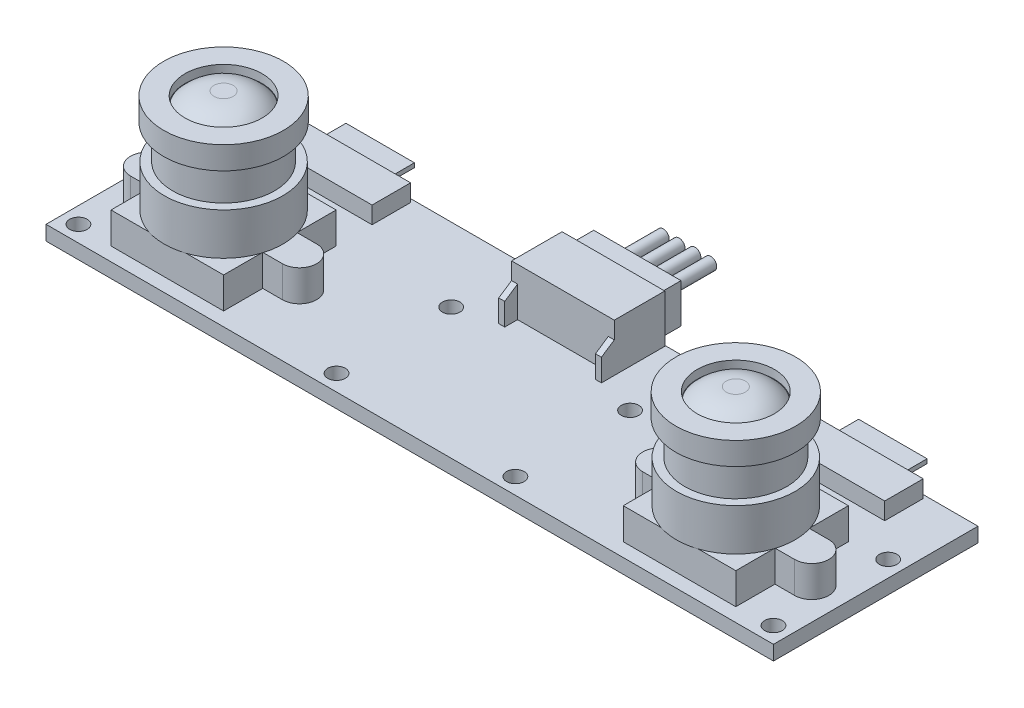
SolidWorks part; units mm, degrees
ref_plane "Front" through (0, 0, 0) normal (0, 0, 1) x (1, 0, 0)
ref_plane "Top" through (0, 0, 0) normal (0, 1, 0) x (1, 0, 0)
ref_plane "Right" through (0, 0, 0) normal (1, 0, 0) x (0, 0, -1)
sketch "Sketch1" plane through (0, 0, 0) normal (0, 1, 0) x (1, 0, 0)
  line L1 (-42.5, -11.95) -> (42.5, -11.95)
  line L2 (-42.5, -11.95) -> (-42.5, 11.95)
  line L3 (-42.5, 11.95) -> (42.5, 11.95)
  line L4 (42.5, -11.95) -> (42.5, 11.95)
  line L5 (-42.5, -11.95) -> (42.5, 11.95) construction
  line L6 (-42.5, 11.95) -> (42.5, -11.95) construction
  point P0 (0, 0)
  dimension "D1" = 23.9
  dimension "D2" = 85
extrude "Boss-Extrude1" add sketch "Sketch1" along normal blind 1.7
sketch "Sketch2" plane through (0, 1.7, 0) normal (0, 1, 0) x (1, 0, 0)
  line L0 (40.605, -11.08) -> (40.605, -11.95) construction
  line L1 (-40.605, -10.055) -> (40.605, -10.055) construction
  line L2 (-40.605, -10.055) -> (-40.605, 3.345) construction
  line L3 (-40.605, 3.345) -> (40.605, 3.345) construction
  line L5 (-40.605, -10.055) -> (40.605, 3.345) construction
  line L6 (-40.605, 3.345) -> (40.605, -10.055) construction
  line L7 (-10.45, -10.055) -> (10.45, -10.055) construction
  line L8 (-10.45, -10.055) -> (-10.45, 3.345) construction
  line L9 (-10.45, 3.345) -> (10.45, 3.345) construction
  line L10 (10.45, -10.055) -> (10.45, 3.345) construction
  line L11 (-10.45, -10.055) -> (10.45, 3.345) construction
  line L12 (-10.45, 3.345) -> (10.45, -10.055) construction
  line L14 (-42.5, -11.95) -> (42.5, -11.95) construction
  line L16 (41.63, -10.055) -> (42.5, -10.055) construction
  line L17 (42.5, -11.95) -> (42.5, 11.95) construction
  line L18 (-9.425, 3.345) -> (9.425, 3.345) construction
  line L19 (40.605, 2.32) -> (40.605, -9.03) construction
  circle A0 centre (-40.605, 3.345) radius 1.025
  circle A1 centre (-10.45, 3.345) radius 1.025
  circle A2 centre (-40.605, -10.055) radius 1.025
  circle A3 centre (-10.45, -10.055) radius 1.025
  circle A4 centre (10.45, 3.345) radius 1.025
  circle A5 centre (40.605, 3.345) radius 1.025
  circle A6 centre (40.605, -10.055) radius 1.025
  circle A7 centre (10.45, -10.055) radius 1.025
  point P0 (0, -3.355)
  point P5 (0, -3.355)
  dimension "D1" = 2.05
  dimension "D2" = 0.87
  dimension "D3" = 18.85
  dimension "D4" = 11.35
extrude "Cut-Extrude1" cut sketch "Sketch2" against normal through all
sketch "Sketch3" plane through (0, 1.7, 0) normal (0, 1, 0) x (1, 0, 0)
  line L0 (42.5, 11.95) -> (-42.5, 11.95) construction
  line L1 (-6, 5.95) -> (6, 5.95)
  line L2 (-6, 5.95) -> (-6, 11.95)
  line L3 (-6, 11.95) -> (6, 11.95)
  line L4 (6, 5.95) -> (6, 11.95)
  line L5 (-6, 5.95) -> (6, 11.95) construction
  line L6 (-6, 11.95) -> (6, 5.95) construction
  point P0 (0, 8.95)
  point P7 (6.8289, 3.9107)
  point P8 (0, 0)
  point P10 (6.1915, 4.9199)
  dimension "D1" = 12
  dimension "D2" = 6
extrude "Boss-Extrude2" add sketch "Sketch3" along normal blind 5.6
sketch "Sketch4" plane through (0, 1.7, 0) normal (0, 1, 0) x (1, 0, 0)
  line L1 (-6, 5.95) -> (-5.3, 5.95)
  line L2 (-6, 5.95) -> (-6, 4.45)
  line L3 (-6, 4.45) -> (-5.3, 4.45)
  line L4 (-5.3, 5.95) -> (-5.3, 4.45)
  line L5 (6, 5.95) -> (5.3, 5.95)
  line L6 (6, 5.95) -> (6, 4.45)
  line L7 (6, 4.45) -> (5.3, 4.45)
  line L8 (5.3, 5.95) -> (5.3, 4.45)
  point P10 (-4.2956, 2.7892)
  dimension "D1" = 0.7
  dimension "D2" = 1.5
extrude "Boss-Extrude3" add sketch "Sketch4" along normal blind 3.6
chamfer "Chamfer1" distance 1 distance2 1.5 2 edges at (-5.65, 5.3, -4.45) (5.65, 5.3, -4.45) first distance on face at (-5.65, 3.5, -4.45) first distance on face at (5.65, 3.5, -4.45)
sketch "Sketch5" plane through (0, 0, -11.95) normal (0, 0, -1) x (-1, 0, 0)
  line L1 (6, 7.3) -> (-6, 7.3)
  line L2 (6, 7.3) -> (6, 1.7)
  line L3 (6, 1.7) -> (-6, 1.7)
  line L4 (-6, 7.3) -> (-6, 1.7)
extrude "Cut-Extrude2" cut sketch "Sketch5" against normal blind 0.1
sketch "Sketch6" plane through (0, 0, -11.85) normal (0, 0, -1) x (-1, 0, 0)
  line L1 (-5.1, 6.5) -> (5.1, 6.5)
  line L2 (-5.1, 6.5) -> (-5.1, 1.9)
  line L3 (-5.1, 1.9) -> (5.1, 1.9)
  line L4 (5.1, 6.5) -> (5.1, 1.9)
  line L5 (-42.5, 1.7) -> (42.5, 1.7) construction
  point P6 (0, 6.5)
  point P8 (4.9342, 6.4389)
  dimension "D1" = 10.2
  dimension "D2" = 4.6
  dimension "D3" = 0.2
extrude "Boss-Extrude4" add sketch "Sketch6" along normal blind 2.8
sketch "Sketch7" plane through (0, 0, -14.65) normal (0, 0, -1) x (-1, 0, 0)
  line L0 (-0.225, 4.2) -> (0.225, 4.2) construction
  line L1 (5.1, 1.9) -> (5.1, 6.5) construction
  line L2 (-2.075, 4.2) -> (-1.625, 4.2) construction
  line L3 (1.625, 4.2) -> (2.075, 4.2) construction
  circle A0 centre (0.925, 4.2) radius 0.7
  circle A1 centre (-0.925, 4.2) radius 0.7
  circle A2 centre (-2.775, 4.2) radius 0.7
  circle A3 centre (2.775, 4.2) radius 0.7
  point P2 (0, 4.2)
  point P7 (5.1, 4.2)
  point P19 (0.987, 4.2)
  point P20 (-1.2862, 4.2)
  point P21 (-0.4479, 4.2)
  dimension "D1" = 1.4
  dimension "D2" = 0.45
extrude "Boss-Extrude5" add sketch "Sketch7" along normal blind 5.8
sketch "Sketch8" plane through (0, 1.7, 0) normal (0, 1, 0) x (1, 0, 0)
  line L0 (0, 0) -> (0, -11.95) construction
  line L1 (-36.5, -10.35) -> (-23.35, -10.35)
  line L2 (-36.5, -10.35) -> (-36.5, -5.775)
  line L3 (-36.5, 2.8) -> (-23.35, 2.8)
  line L4 (-23.35, -10.35) -> (-23.35, -5.775)
  line L9 (-42.5, -11.95) -> (42.5, -11.95) construction
  line L10 (-36.5, -1.775) -> (-38.8, -1.775)
  line L11 (-36.5, -5.775) -> (-38.8, -5.775)
  line L12 (-36.5, -1.775) -> (-36.5, 2.8)
  line L13 (-23.35, -1.775) -> (-21.05, -1.775)
  line L14 (-23.35, -5.775) -> (-21.05, -5.775)
  line L15 (-23.35, -1.775) -> (-23.35, 2.8)
  line L16 (-42.5, 11.95) -> (-42.5, -11.95) construction
  line L17 (23.35, -1.775) -> (23.35, 2.8)
  line L18 (23.35, -5.775) -> (21.05, -5.775)
  line L19 (23.35, -1.775) -> (21.05, -1.775)
  line L20 (36.5, -1.775) -> (36.5, 2.8)
  line L21 (36.5, -5.775) -> (38.8, -5.775)
  line L22 (36.5, -1.775) -> (38.8, -1.775)
  line L23 (23.35, -10.35) -> (23.35, -5.775)
  line L24 (36.5, 2.8) -> (23.35, 2.8)
  line L25 (36.5, -10.35) -> (36.5, -5.775)
  line L26 (36.5, -10.35) -> (23.35, -10.35)
  arc A0 (-38.8, -1.775) -> (-38.8, -5.775) centre (-38.8, -3.775) ccw
  arc A1 (-21.05, -1.775) -> (-21.05, -5.775) centre (-21.05, -3.775) cw
  arc A2 (21.05, -1.775) -> (21.05, -5.775) centre (21.05, -3.775) ccw
  arc A3 (38.8, -1.775) -> (38.8, -5.775) centre (38.8, -3.775) cw
  point P19 (-39.506, -7.79)
  point P20 (0, 0)
  point P21 (-23.0089, -5.9445)
  point P22 (-22.4155, -5.8782)
  point P23 (-23.4638, -5.7921)
  point P24 (-39.3082, -6.1877)
  point P25 (-22.2477, 3.2456)
  point P26 (-19.8451, -2.9943)
  dimension "D1" = 4
  dimension "D2" = 13.15
  dimension "D3" = 13.15
  dimension "D4" = 2.3
  dimension "D5" = 1.6
  dimension "D6" = 6
extrude "Boss-Extrude6" add sketch "Sketch8" along normal blind 3.65
sketch "Sketch9" plane through (0, 5.35, 0) normal (0, 1, 0) x (1, 0, 0)
  line L0 (-23.35, 2.8) -> (-36.5, 2.8) construction
  line L1 (36.5, 2.8) -> (23.35, 2.8) construction
  circle A0 centre (-29.925, -3.775) radius 6.925
  circle A1 centre (29.925, -3.775) radius 6.925
  arc A2 (21.05, -1.775) -> (21.05, -5.775) centre (21.05, -3.775) ccw construction
  point P4 (0, 0)
  point P5 (-31.2965, -5.098)
  point P8 (-29.925, 2.8)
  point P9 (0, 0)
  point P12 (29.925, 2.8)
  point P16 (19.05, -3.775)
  dimension "D1" = 13.85
extrude "Boss-Extrude7" add sketch "Sketch9" along normal blind 4.9
sketch "Sketch10" plane through (0, 10.25, 0) normal (0, 1, 0) x (1, 0, 0)
  circle A0 centre (-29.925, -3.775) radius 5.95
  circle A1 centre (29.925, -3.775) radius 5.95
  dimension "D1" = 11.9
extrude "Boss-Extrude8" add sketch "Sketch10" along normal blind 4
sketch "Sketch11" plane through (0, 14.25, 0) normal (0, 1, 0) x (1, 0, 0)
  circle A0 centre (-29.925, -3.775) radius 7
  circle A1 centre (29.925, -3.775) radius 7
  dimension "D1" = 14
extrude "Boss-Extrude9" add sketch "Sketch11" along normal blind 2.65
sketch "Sketch12" plane through (0, 16.9, 0) normal (0, 1, 0) x (1, 0, 0)
  circle A0 centre (-29.925, -3.775) radius 4.5
  circle A1 centre (29.925, -3.775) radius 4.5
  dimension "D1" = 9
extrude "Cut-Extrude3" cut sketch "Sketch12" against normal blind 1
sketch "Sketch13" plane through (0, 15.9, 0) normal (0, 1, 0) x (1, 0, 0)
  circle A0 centre (-29.925, -3.775) radius 4.45
  circle A1 centre (29.925, -3.775) radius 4.45
  dimension "D1" = 8.9
extrude "Boss-Extrude10" add sketch "Sketch13" along normal blind 1.5
fillet "Fillet1" radius 4.45 2 edges at (-29.925, 17.4, 8.225) (29.925, 17.4, 8.225)
sketch "Sketch14" plane through (0, 1.7, 0) normal (0, 1, 0) x (1, 0, 0)
  line L0 (-36.5, 9.3) -> (-42.5, 9.3) construction
  line L1 (-36.5, 11.55) -> (-23.4, 11.55)
  line L2 (-36.5, 11.55) -> (-36.5, 7.05)
  line L3 (-36.5, 7.05) -> (-23.4, 7.05)
  line L4 (-23.4, 11.55) -> (-23.4, 7.05)
  line L5 (23.4, 11.55) -> (36.5, 11.55)
  line L6 (23.4, 11.55) -> (23.4, 7.05)
  line L7 (23.4, 7.05) -> (36.5, 7.05)
  line L8 (36.5, 11.55) -> (36.5, 7.05)
  line L9 (-42.5, 11.95) -> (-42.5, -11.95) construction
  line L10 (36.5, 9.3) -> (42.5, 9.3) construction
  line L11 (42.5, -11.95) -> (42.5, 11.95) construction
  line L12 (42.5, 11.95) -> (-42.5, 11.95) construction
  point P16 (-22.4119, 10.8073)
  point P17 (-15.8535, 9.8864)
  point P18 (-37.2023, 9.3336)
  point P21 (26.0671, 10.2786)
  point P22 (-38.9141, 7.05)
  dimension "D1" = 13.1
  dimension "D2" = 4.5
  dimension "D3" = 0.4
  dimension "D4" = 6
extrude "Boss-Extrude11" add sketch "Sketch14" along normal blind 2
sketch "Sketch15" plane through (0, 0, -11.55) normal (0, 0, -1) x (-1, 0, 0)
  line L0 (23.4, 3.7) -> (36.5, 3.7) construction
  line L1 (-33.95, 2.95) -> (-25.95, 2.95)
  line L2 (-33.95, 2.95) -> (-33.95, 2.45)
  line L3 (-33.95, 2.45) -> (-25.95, 2.45)
  line L4 (-25.95, 2.95) -> (-25.95, 2.45)
  line L5 (25.95, 2.95) -> (33.95, 2.95)
  line L6 (25.95, 2.95) -> (25.95, 2.45)
  line L7 (25.95, 2.45) -> (33.95, 2.45)
  line L8 (33.95, 2.95) -> (33.95, 2.45)
  line L9 (-36.5, 3.7) -> (-23.4, 3.7) construction
  line L10 (-23.4, 3.7) -> (-23.4, 1.7) construction
  point P8 (29.95, 2.95)
  point P11 (29.95, 3.7)
  point P12 (-29.95, 2.95)
  point P15 (-29.95, 3.7)
  point P16 (-35.4653, 3.1249)
  point P17 (-35.739, 2.2619)
  point P18 (-25.95, 2.7)
  point P21 (-23.4, 2.7)
  point P22 (-24.1278, 2.9861)
  dimension "D1" = 0.5
  dimension "D2" = 8
extrude "Boss-Extrude12" add sketch "Sketch15" along normal blind 3
